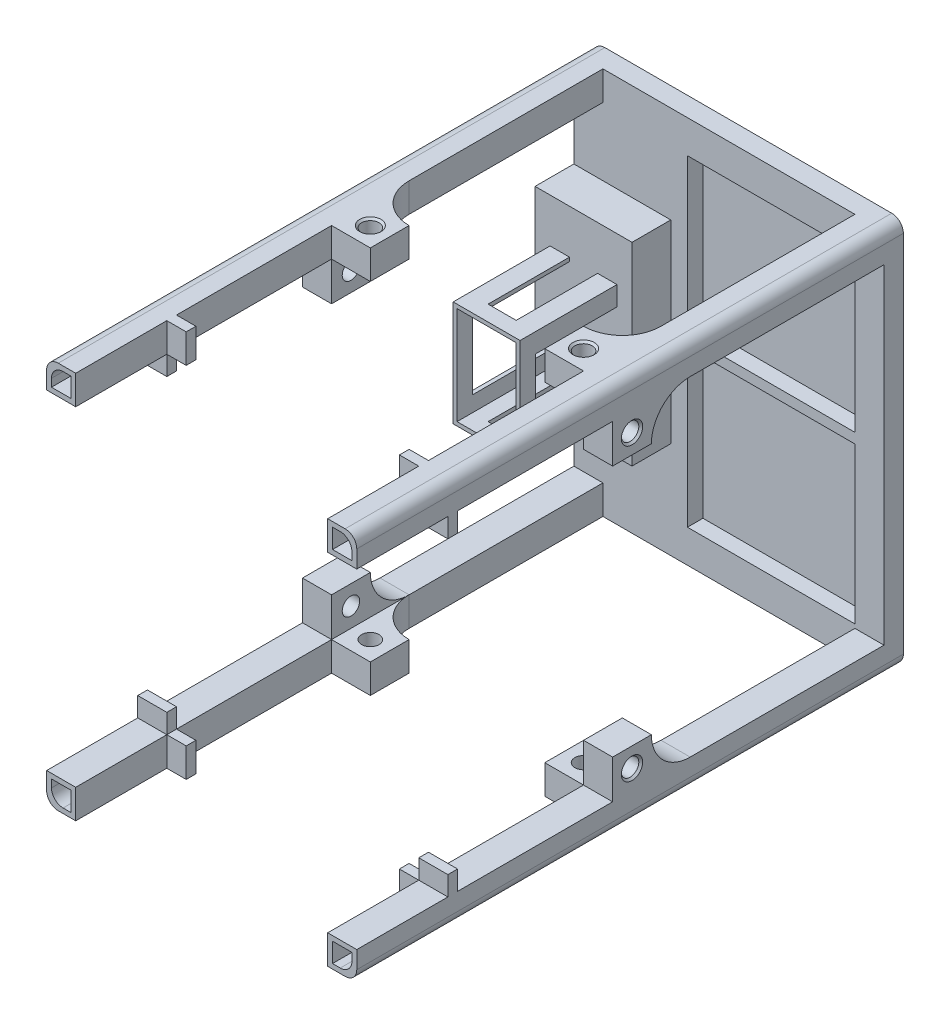
SolidWorks part; units mm, degrees
material "Alliage 1060"
ref_plane "Plan de dessus" through (0, 0, 0) normal (0, 0, 1) x (1, 0, 0)
ref_plane "Plan de droite" through (0, 0, 0) normal (0, 1, 0) x (1, 0, 0)
ref_plane "Plan de face" through (0, 0, 0) normal (1, 0, 0) x (0, 0, -1)
sketch "Esquisse1" plane through (0, 0, 0) normal (0, 0, 1) x (1, 0, 0)
  line L1 (0, 0) -> (-80, 0)
  line L2 (0, 0) -> (0, -100)
  line L3 (0, -100) -> (-80, -100)
  line L4 (-80, 0) -> (-80, -100)
  dimension "D1" = 80
  dimension "D2" = 100
extrude "Boss.-Extru.1" add sketch "Esquisse1" along normal blind 5
sketch "Esquisse4" plane through (0, 0, 5) normal (0, 0, 1) x (1, 0, 0)
  line L0 (-40, 0) -> (-40, -100) construction
  line L1 (-80, 0) -> (-72.5, 0)
  line L2 (-80, 0) -> (-80, -7.5)
  line L3 (-80, -7.5) -> (-72.5, -7.5)
  line L4 (-72.5, 0) -> (-72.5, -7.5)
  line L5 (0, 0) -> (-80, 0) construction
  line L6 (-80, -100) -> (0, -100) construction
  line L7 (-80, -50) -> (0, -50) construction
  line L8 (-80, 0) -> (-80, -100) construction
  line L9 (0, -100) -> (0, 0) construction
  line L22 (-1.25, -6.25) -> (-1.25, -4.25)
  line L23 (-73.75, -6.25) -> (-78.75, -6.25)
  line L24 (-73.75, -6.25) -> (-73.75, -1.25)
  line L25 (-73.75, -1.25) -> (-75.75, -1.25)
  line L26 (-78.75, -6.25) -> (-78.75, -4.25)
  line L27 (-6.25, -1.25) -> (-4.25, -1.25)
  line L28 (-6.25, -6.25) -> (-6.25, -1.25)
  line L29 (-6.25, -6.25) -> (-1.25, -6.25)
  line L30 (-7.5, 0) -> (-7.5, -7.5)
  line L31 (0, -7.5) -> (-7.5, -7.5)
  line L32 (0, 0) -> (0, -7.5)
  line L33 (0, 0) -> (-7.5, 0)
  line L34 (0, -100) -> (-7.5, -100)
  line L35 (0, -100) -> (0, -92.5)
  line L36 (0, -92.5) -> (-7.5, -92.5)
  line L37 (-7.5, -100) -> (-7.5, -92.5)
  line L38 (-6.25, -93.75) -> (-1.25, -93.75)
  line L39 (-6.25, -93.75) -> (-6.25, -98.75)
  line L40 (-6.25, -98.75) -> (-4.25, -98.75)
  line L41 (-78.75, -93.75) -> (-78.75, -95.75)
  line L42 (-73.75, -98.75) -> (-75.75, -98.75)
  line L43 (-73.75, -93.75) -> (-73.75, -98.75)
  line L44 (-73.75, -93.75) -> (-78.75, -93.75)
  line L45 (-1.25, -93.75) -> (-1.25, -95.75)
  line L46 (-72.5, -100) -> (-72.5, -92.5)
  line L47 (-80, -92.5) -> (-72.5, -92.5)
  line L48 (-80, -100) -> (-80, -92.5)
  line L49 (-80, -100) -> (-72.5, -100)
  arc A0 (-78.75, -95.75) -> (-75.75, -98.75) centre (-75.75, -95.75) ccw
  arc A1 (-4.25, -98.75) -> (-1.25, -95.75) centre (-4.25, -95.75) ccw
  arc A2 (-1.25, -4.25) -> (-4.25, -1.25) centre (-4.25, -4.25) ccw
  arc A3 (-78.75, -4.25) -> (-75.75, -1.25) centre (-75.75, -4.25) cw
  point P47 (-78.75, -98.75)
  point P50 (-1.25, -98.75)
  point P53 (-1.25, -1.25)
  point P56 (-78.75, -1.25)
  dimension "D7" = 3
  dimension "D1" = 7.5
  dimension "D2" = 7.5
  dimension "D3" = 5
  dimension "D4" = 5
  dimension "D5" = 1.25
  dimension "D6" = 1.25
extrude "Boss.-Extru.3" add sketch "Esquisse4" along normal blind 136
sketch "Esquisse22" plane through (0, -7.5, 0) normal (0, -1, 0) x (1, 0, 0)
  line L0 (-80, 0) -> (-80, 75) construction
  line L1 (-80, 141) -> (-80, 0) construction
  line L2 (-80, 75) -> (-72.5, 75)
  line L3 (-72.5, 141) -> (-72.5, 5) construction
  line L6 (-40, 0) -> (-40, 132.5941) construction
  line L7 (-80, 0) -> (0, 0) construction
  line L8 (0, 75) -> (-7.5, 75)
  line L11 (-80, 65) -> (-72.5, 65)
  line L12 (-72.5, 65) -> (-72.5, 75)
  line L13 (-80, 65) -> (-80, 75)
  line L14 (-7.5, 65) -> (0, 65)
  line L15 (-7.5, 141) -> (-7.5, 5) construction
  line L16 (0, 141) -> (0, 0) construction
  line L17 (0, 65) -> (0, 75)
  line L18 (-7.5, 75) -> (-7.5, 65)
  dimension "D1" = 75
  dimension "D2" = 10
  dimension "D3" = 10
extrude "Boss.-Extru.4" add sketch "Esquisse22" along normal blind 10
sketch "Esquisse27" plane through (0, -92.5, 0) normal (0, 1, 0) x (1, 0, 0)
  line L17 (0, 0) -> (0, -75) construction
  line L18 (0, -75) -> (-7.5, -75)
  line L19 (-40, 0) -> (-40, -132.5941) construction
  line L20 (-80, -75) -> (-72.5, -75)
  line L21 (0, -65) -> (-7.5, -65)
  line L22 (-7.5, -65) -> (-7.5, -75)
  line L23 (0, -65) -> (0, -75)
  line L24 (-72.5, -65) -> (-80, -65)
  line L25 (-80, -65) -> (-80, -75)
  line L26 (-72.5, -75) -> (-72.5, -65)
  dimension "D1" = 75
  dimension "D2" = 10
  dimension "D3" = 10
extrude "Boss.-Extru.5" add sketch "Esquisse27" along normal blind 10
sketch "Esquisse28" plane through (-72.5, 0, 0) normal (1, 0, 0) x (0, 0, -1)
  line L0 (0, -100) -> (0, 0) construction
  line L1 (-65, 0) -> (-75, 0)
  line L5 (0, -100) -> (-75, -100) construction
  line L6 (-65, 0) -> (-65, -7.5)
  line L7 (-75, -100) -> (-75, -92.5)
  line L14 (-65, -7.5) -> (-75, -7.5)
  line L20 (0, -50) -> (-132.5941, -50) construction
  line L22 (-65, -100) -> (-65, -92.5)
  line L23 (-65, -92.5) -> (-75, -92.5)
  line L24 (-65, -100) -> (-75, -100)
  line L28 (-75, 0) -> (-75, -7.5)
  point P2 (0, -50)
  dimension "D1" = 0
  dimension "D2" = 75
  dimension "D3" = 10
extrude "Boss.-Extru.6" add sketch "Esquisse28" along normal blind 10
sketch "Esquisse29" plane through (-7.5, 0, 0) normal (-1, 0, 0) x (0, 0, 1)
  line L0 (65, -100) -> (75, -100)
  line L1 (0, 0) -> (75, 0) construction
  line L2 (65, -100) -> (65, -92.5)
  line L3 (75, 0) -> (75, -7.5)
  line L4 (65, -92.5) -> (75, -92.5)
  line L5 (0, -50) -> (132.5941, -50) construction
  line L6 (65, 0) -> (65, -7.5)
  line L7 (65, -7.5) -> (75, -7.5)
  line L8 (65, 0) -> (75, 0)
  line L9 (75, -100) -> (75, -92.5)
  dimension "D1" = 75
  dimension "D2" = 10
extrude "Boss.-Extru.7" add sketch "Esquisse29" along normal blind 10
sketch "Esquisse31" plane through (0, 0, 5) normal (0, 0, 1) x (1, 0, 0)
  line L0 (-7.5, -91.5) -> (-50.7, -91.5)
  line L1 (-7.5, -91.5) -> (-7.5, -51.3)
  line L2 (-7.5, -51.3) -> (-50.7, -51.3)
  line L3 (-50.7, -91.5) -> (-50.7, -51.3)
  line L8 (0, -100) -> (-80, 0) construction
  line L9 (-80, -100) -> (0, 0) construction
  line L15 (-80, -50) -> (0, -50) construction
  line L16 (-80, -7.5) -> (-80, -92.5) construction
  line L17 (0, -92.5) -> (0, -7.5) construction
  line L18 (-7.5, -8.5) -> (-7.5, -48.7)
  line L19 (-7.5, -48.7) -> (-50.7, -48.7)
  line L20 (-50.7, -8.5) -> (-50.7, -48.7)
  line L21 (-7.5, -8.5) -> (-50.7, -8.5)
  line L22 (-40, -100) -> (-40, 0) construction
  line L23 (-72.5, -100) -> (-7.5, -100) construction
  line L24 (-7.5, 0) -> (-72.5, 0) construction
  point P28 (-7.5, -100)
  dimension "D1" = 1.3
  dimension "D2" = 40.2
  dimension "D3" = 43.2
extrude "Enlèv. mat.-Extru.4" cut sketch "Esquisse31" against normal blind 4
sketch "Esquisse32" plane through (0, 0, 0) normal (1, 0, 0) x (0, 0, -1)
  line L0 (-5, -92.5) -> (-5, -7.5) construction
  line L1 (-70, -17.5) -> (-70, -2.5112) construction
  line L2 (-65, -17.5) -> (-75, -17.5) construction
  line L3 (-75, -12.5) -> (-54.5965, -12.5) construction
  line L4 (-75, -17.5) -> (-75, -7.5) construction
  line L5 (-5, -50) -> (-194.7584, -50) construction
  circle A0 centre (-70, -12.5) radius 2.25
  circle A1 centre (-70, -87.5) radius 2.25
  dimension "D1" = 4.5
extrude "Enlèv. mat.-Extru.5" cut sketch "Esquisse32" against normal through all
sketch "Esquisse33" plane through (0, -100, 0) normal (0, -1, 0) x (1, 0, 0)
  line L0 (-72.5, 75) -> (-72.5, 65) construction
  line L1 (-62.5, 65) -> (-72.5, 65) construction
  line L2 (-72.5, 65) -> (-72.5, 5) construction
  line L3 (-72.5, 70) -> (-62.5, 70) construction
  line L6 (-40, 0) -> (-40, 137.1493) construction
  line L8 (-80, 0) -> (0, 0) construction
  circle A0 centre (-67.5, 70) radius 2.25
  circle A2 centre (-12.5, 70) radius 2.25
  dimension "D1" = 4.5
extrude "Enlèv. mat.-Extru.6" cut sketch "Esquisse33" against normal through all
chamfer "Chanfrein1" distance 0.5 angle 45 8 edges at (-80, -10.25, 70) (-65.25, -100, 70) (0, -89.75, 70) (0, -10.25, 70) (-65.25, 0, 70) (-80, -89.75, 70) (-14.75, -100, 70) (-14.75, 0, 70)
fillet "Congé1" radius 10 4 edges at (-7.5, -3.75, 65) (-72.5, -3.75, 65) (-7.5, -96.25, 65) (-72.5, -96.25, 65)
fillet "Congé2" radius 10 4 edges at (-76.25, -7.5, 65) (-3.75, -7.5, 65) (-76.25, -92.5, 65) (-3.75, -92.5, 65)
sketch "Esquisse37" plane through (0, 0, 5) normal (0, 0, 1) x (1, 0, 0)
  line L0 (-80, -50) -> (0, -50) construction
  line L3 (-80, -7.5) -> (-80, -92.5) construction
  line L6 (0, -92.5) -> (0, -7.5) construction
  line L7 (-55, -75) -> (-80, -75)
  line L8 (-55, -75) -> (-55, -25)
  line L9 (-55, -25) -> (-80, -25)
  line L10 (-80, -75) -> (-80, -25)
  point P6 (-80, -50)
  dimension "D1" = 50
  dimension "D2" = 25
  dimension "D3" = 0
  dimension "D4" = 0
extrude "Boss.-Extru.8" add sketch "Esquisse37" along normal blind 10
fillet "Congé3" radius 3 4 edges at (-80, -100, 70.5) (0, -100, 70.5) (0, 0, 70.5) (-80, 0, 70.5)
sketch "Esquisse42" plane through (0, 0, 0) normal (0, 0, -1) x (-1, 0, 0)
  line L0 (67.5, -27.5) -> (67.5, -72.5) construction
  line L1 (56.5, -50) -> (78.5, -50) construction
  line L2 (78.5, -50) -> (80, -50) construction
  circle A0 centre (67.5, -43.25) radius 1.11
  circle A1 centre (67.5, -56.75) radius 1.11
  point P3 (67.5, -50)
  dimension "D1" = 2.22
  dimension "D2" = 6.75
extrude "Enlèv. mat.-Extru.7" cut sketch "Esquisse42" against normal blind 14.5
sketch "Esquisse43" plane through (0, -7.5, 0) normal (0, -1, 0) x (1, 0, 0)
  line L0 (-72.5, 141) -> (-72.5, 75) construction
  line L1 (-72.5, 117.5) -> (-80, 117.5)
  line L2 (-72.5, 117.5) -> (-72.5, 115)
  line L3 (-72.5, 115) -> (-80, 115)
  line L4 (-80, 117.5) -> (-80, 115)
  line L5 (-80, 0) -> (-80, 141) construction
  line L6 (-62.5, 75) -> (-72.5, 75) construction
  line L7 (-40, 5) -> (-40, 158.167) construction
  line L8 (-72.5, 5) -> (-7.5, 5) construction
  line L9 (0, 117.5) -> (0, 115)
  line L10 (-7.5, 117.5) -> (-7.5, 115)
  line L11 (-7.5, 117.5) -> (0, 117.5)
  line L12 (-7.5, 115) -> (0, 115)
  dimension "D1" = 2.5
  dimension "D2" = 40
extrude "Boss.-Extru.9" add sketch "Esquisse43" along normal blind 5
sketch "Esquisse44" plane through (0, -92.5, 0) normal (0, 1, 0) x (1, 0, 0)
  line L4 (-72.5, -141) -> (-72.5, -75) construction
  line L9 (-72.5, -115) -> (-80, -115)
  line L10 (-72.5, -115) -> (-72.5, -117.5)
  line L11 (-72.5, -117.5) -> (-80, -117.5)
  line L12 (-80, -115) -> (-80, -117.5)
  line L13 (-80, -141) -> (-80, 0) construction
  line L14 (-62.5, -75) -> (-72.5, -75) construction
  line L15 (-40, -5) -> (-40, -141) construction
  line L16 (-7.5, -5) -> (-72.5, -5) construction
  line L17 (0, -115) -> (0, -117.5)
  line L18 (-7.5, -117.5) -> (0, -117.5)
  line L19 (-7.5, -115) -> (-7.5, -117.5)
  line L20 (-7.5, -115) -> (0, -115)
  dimension "D2" = 2.5
  dimension "D3" = 40
extrude "Boss.-Extru.10" add sketch "Esquisse44" along normal blind 5
sketch "Esquisse45" plane through (-72.5, 0, 0) normal (1, 0, 0) x (0, 0, -1)
  line L0 (-141, 0) -> (0, 0) construction
  line L1 (-115, -7.5) -> (-117.5, -7.5)
  line L2 (-115, -7.5) -> (-115, 0)
  line L3 (-115, 0) -> (-117.5, 0)
  line L4 (-117.5, -7.5) -> (-117.5, 0)
  line L5 (-5, -50) -> (-180.7635, -50) construction
  line L6 (-5, -92.5) -> (-5, -7.5) construction
  line L7 (-117.5, -92.5) -> (-117.5, -100)
  line L8 (-115, -100) -> (-117.5, -100)
  line L9 (-115, -92.5) -> (-115, -100)
  line L10 (-115, -92.5) -> (-117.5, -92.5)
  dimension "D1" = 2.5
extrude "Boss.-Extru.11" add sketch "Esquisse45" along normal blind 5
sketch "Esquisse46" plane through (-7.5, 0, 0) normal (-1, 0, 0) x (0, 0, 1)
  line L0 (0, 0) -> (141, 0) construction
  line L1 (115, 0) -> (117.5, 0)
  line L2 (115, 0) -> (115, -7.5)
  line L3 (115, -7.5) -> (117.5, -7.5)
  line L4 (117.5, 0) -> (117.5, -7.5)
  line L5 (115, -7.5) -> (75, -7.5) construction
  line L6 (15, -50) -> (141.2529, -50) construction
  line L7 (15, -25) -> (15, -75) construction
  line L8 (75, -17.5) -> (75, -7.5) construction
  line L9 (117.5, -100) -> (117.5, -92.5)
  line L10 (115, -92.5) -> (117.5, -92.5)
  line L11 (115, -100) -> (115, -92.5)
  line L12 (115, -100) -> (117.5, -100)
  dimension "D1" = 2.5
  dimension "D2" = 40
extrude "Boss.-Extru.12" add sketch "Esquisse46" along normal blind 5
sketch "Esquisse47" plane through (0, 0, 15) normal (0, 0, 1) x (1, 0, 0)
  line L0 (-55, -25) -> (-80, -25) construction
  line L1 (-80, -25) -> (-80, -75) construction
  line L2 (-80, -75) -> (-55, -75) construction
  line L3 (-55, -75) -> (-55, -25) construction
  line L5 (-75.125, -37.375) -> (-59.875, -37.375)
  line L6 (-75.125, -37.375) -> (-75.125, -62.625)
  line L7 (-75.125, -62.625) -> (-59.875, -62.625)
  line L8 (-59.875, -37.375) -> (-59.875, -62.625)
  line L12 (-75.8865, -36.375) -> (-58.875, -36.375)
  line L13 (-76.125, -36.375) -> (-76.125, -63.625)
  line L14 (-76.125, -63.625) -> (-58.875, -63.625)
  line L15 (-58.875, -63.625) -> (-58.875, -36.375)
  line L16 (-75.8865, -36.375) -> (-76.125, -36.375)
  dimension "D1" = 15.25
  dimension "D2" = 25.25
  dimension "D3" = 12.375
  dimension "D4" = 9.75
  dimension "D5" = 1
  dimension "D6" = 1
  dimension "D7" = 1
  dimension "D8" = 1
extrude "Boss.-Extru.13" add sketch "Esquisse47" along normal blind 25
sketch "Esquisse48" plane through (-76.125, 0, 0) normal (-1, 0, 0) x (0, 0, 1)
  line L0 (15, -36.375) -> (15, -63.625) construction
  line L1 (15, -41.375) -> (36, -41.375)
  line L2 (15, -41.375) -> (15, -58.625)
  line L3 (15, -58.625) -> (36, -58.625)
  line L4 (36, -41.375) -> (36, -58.625)
  line L6 (40, -36.375) -> (15, -36.375) construction
  dimension "D1" = 17.25
  dimension "D2" = 5
  dimension "D3" = 21
extrude "Enlèv. mat.-Extru.8" cut sketch "Esquisse48" against normal through all
sketch "Esquisse50" plane through (0, -36.375, 0) normal (0, 1, 0) x (1, 0, 0)
  line L0 (-55, -15) -> (-80, -15) construction
  line L1 (-63.875, -15) -> (-71.125, -15)
  line L2 (-63.875, -15) -> (-63.875, -36)
  line L3 (-63.875, -36) -> (-71.125, -36)
  line L4 (-71.125, -15) -> (-71.125, -36)
  line L6 (-58.875, -40) -> (-58.875, -15) construction
  dimension "D1" = 21
  dimension "D2" = 7.25
  dimension "D3" = 5
extrude "Enlèv. mat.-Extru.9" cut sketch "Esquisse50" against normal blind 35
